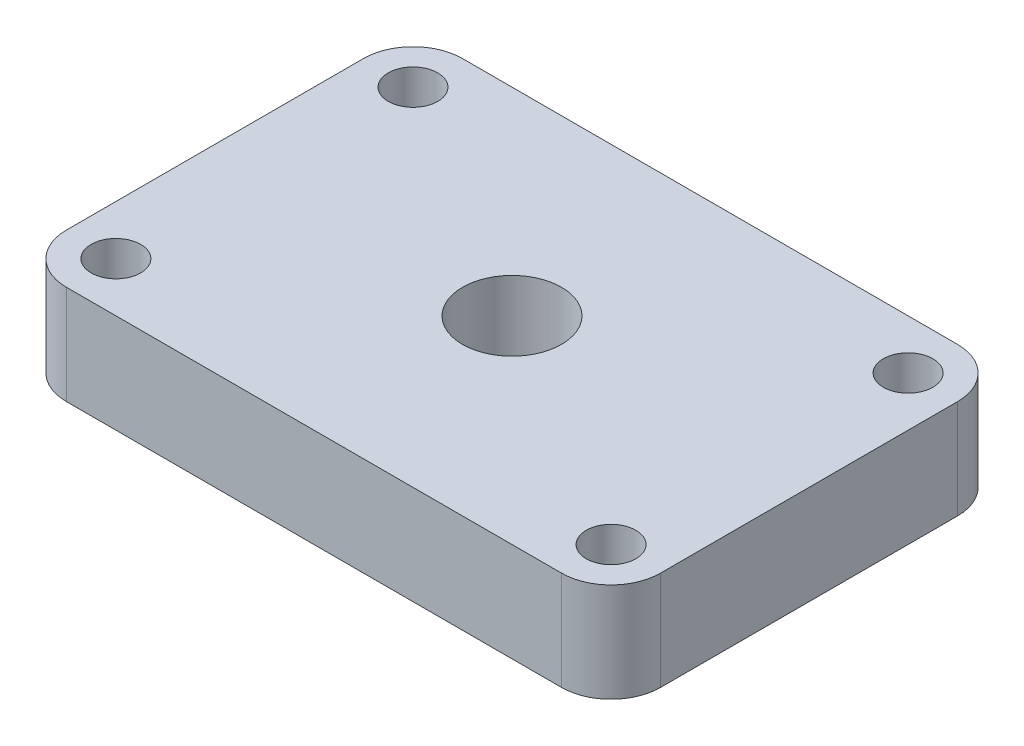
SolidWorks part; units mm, degrees
ref_plane "Front Plane" through (0, 0, 0) normal (0, 0, 1) x (1, 0, 0)
ref_plane "Top Plane" through (0, 0, 0) normal (0, 1, 0) x (1, 0, 0)
ref_plane "Right Plane" through (0, 0, 0) normal (1, 0, 0) x (0, 0, -1)
sketch "Sketch1" plane through (0, 0, 0) normal (0, 1, 0) x (1, 0, 0)
  line L0 (5, 5) -> (55, 35) construction
  line L1 (0, 0) -> (60, 0)
  line L2 (0, 0) -> (0, 40)
  line L3 (0, 40) -> (60, 40)
  line L4 (60, 0) -> (60, 40)
  line L5 (5, 35) -> (55, 35) construction
  line L6 (5, 35) -> (5, 5) construction
  line L7 (5, 5) -> (55, 5) construction
  line L8 (55, 35) -> (55, 5) construction
  line L9 (5, 35) -> (0, 40) construction
  line L10 (55, 35) -> (60, 40) construction
  line L11 (5, 5) -> (0, 0) construction
  line L12 (55, 5) -> (60, 0) construction
  circle A0 centre (5, 35) radius 2.5
  circle A1 centre (55, 35) radius 2.5
  circle A2 centre (55, 5) radius 2.5
  circle A3 centre (5, 5) radius 2.5
  circle A4 centre (30, 20) radius 5
  dimension "D7" = 5
  dimension "D8" = 10
  dimension "D1" = 40
  dimension "D2" = 60
  dimension "D4" = 5
extrude "Boss-Extrude1" add sketch "Sketch1" along normal blind 10
fillet "Fillet1" radius 5 4 edges at (0, 5, -40) (60, 5, -40) (0, 5, 0) (60, 5, 0)
